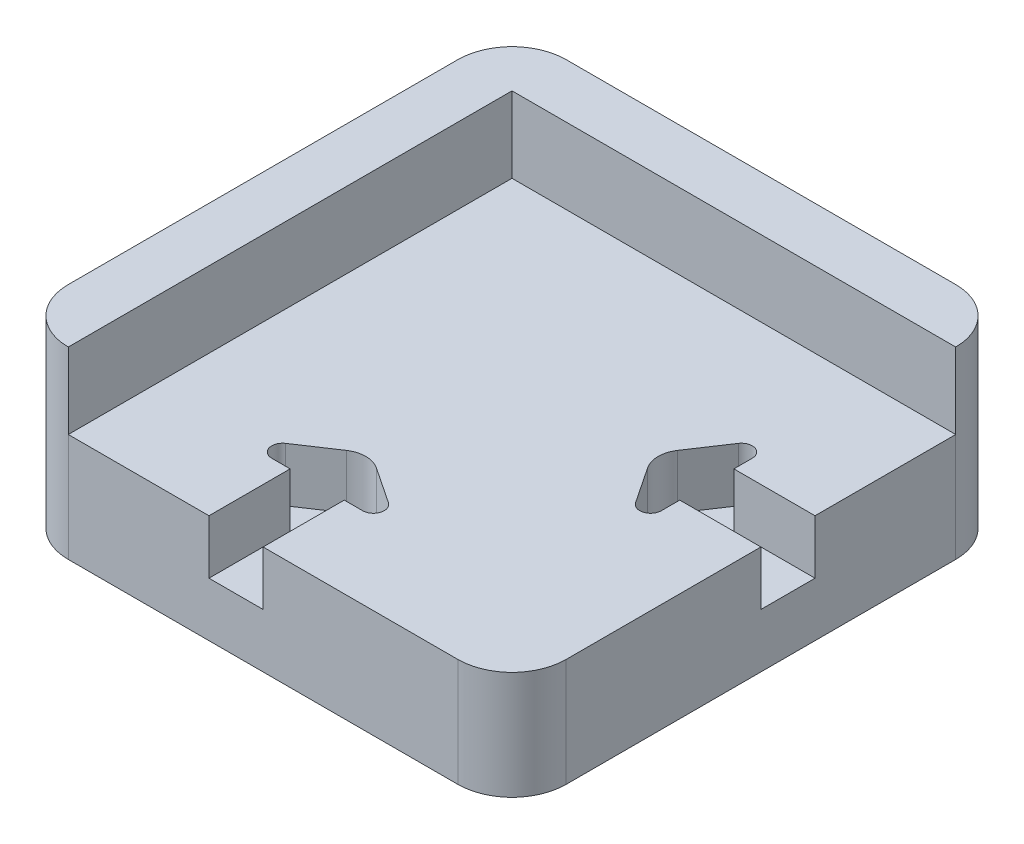
SolidWorks part; units mm, degrees
ref_plane "Front Plane" through (0, 0, 0) normal (0, 0, 1) x (1, 0, 0)
ref_plane "Top Plane" through (0, 0, 0) normal (0, 1, 0) x (1, 0, 0)
ref_plane "Right Plane" through (0, 0, 0) normal (1, 0, 0) x (0, 0, -1)
sketch "Sketch1" plane through (0, 0, 0) normal (0, 1, 0) x (1, 0, 0)
  line L1 (-35.4665, 19.9989) -> (56.5335, 19.9989)
  line L2 (-35.4665, 19.9989) -> (-35.4665, -72.0011)
  line L3 (-35.4665, -72.0011) -> (56.5335, -72.0011)
  line L4 (56.5335, 19.9989) -> (56.5335, -72.0011)
  line L5 (-35.4665, 19.9989) -> (-25.4665, 19.9989)
  line L6 (-35.4665, 19.9989) -> (-35.4665, -72.0011)
  line L7 (-35.4665, -72.0011) -> (-25.4665, -72.0011)
  line L8 (-25.4665, 19.9989) -> (-25.4665, -72.0011)
  line L9 (-35.4665, 19.9989) -> (56.5335, 19.9989)
  line L10 (-35.4665, 19.9989) -> (-35.4665, 9.9989)
  line L11 (-35.4665, 9.9989) -> (56.5335, 9.9989)
  line L12 (56.5335, 19.9989) -> (56.5335, 9.9989)
  dimension "D1" = 92
  dimension "D2" = 92
  dimension "D3" = 10
  dimension "D4" = 10
extrude "Boss-Extrude1" add sketch "Sketch1" along normal blind 20 contours L11 L8 L3 L4 | L8 L11 L4 L1 | L2 L11 L8 L1 | L11 L6 L3 L8 region at (-30.4665, 0, -14.9989) region at (15.5335, 0, -14.9989) region at (-30.4665, 0, 31.0011) region at (15.5335, 0, 31.0011)
extrude "Boss-Extrude2" add sketch "Sketch1<3>" along normal blind 34 contours L11 L6 L3 L8 | L2 L11 L8 L1 | L8 L11 L4 L1 region at (-30.4665, 0, -14.9989) region at (15.5335, 0, -14.9989) region at (-30.4665, 0, 31.0011)
sketch "Sketch1<3>" plane through (0, 0, 0) normal (0, 1, 0) x (1, 0, 0) same geometry as "Sketch1"
fillet "Fillet1" radius 10 4 edges at (56.5335, 17, -19.9989) (-35.4665, 17, -19.9989) (-35.4665, 17, 72.0011) (56.5335, 10, 72.0011)
sketch "Sketch5" plane through (0, 20, 0) normal (0, 1, 0) x (1, 0, 0)
  line L0 (-25.4665, -72.0011) -> (46.5335, -72.0011) construction
  line L1 (10.5335, -72.0011) -> (0.5335, -72.0011)
  line L2 (10.5335, -72.0011) -> (10.5335, -57.0011)
  line L3 (10.5335, -57.0011) -> (0.5335, -57.0011)
  line L4 (0.5335, -72.0011) -> (0.5335, -57.0011)
  line L5 (5.5335, -57.0011) -> (5.5335, -47.0011)
  line L6 (0.5335, -57.0011) -> (-9.4665, -57.0011)
  line L7 (-9.4665, -57.0011) -> (5.5335, -47.0011)
  line L8 (10.5335, -57.0011) -> (20.5321, -57.0011)
  line L9 (20.5321, -57.0011) -> (5.5335, -47.0011)
  line M5 (-25.4665, -72.0011) -> (46.5335, -72.0011)
  dimension "D1" = 15
  dimension "D2" = 10
  dimension "D3" = 10
  dimension "D4" = 10
extrude "Cut-Extrude2" cut sketch "Sketch5" against normal blind 10 contours L8 L9 L5 L3 | L7 L6 L3 L5 | L4 L2 L3 M5 region at (5.5335, 20, 64.5011) region at (10.533, 20, 53.6677) region at (0.5335, 20, 53.6677)
sketch "Sketch6" plane through (0, 20, 0) normal (0, 1, 0) x (1, 0, 0)
  line L0 (56.5335, 9.9989) -> (56.5335, -62.0011) construction
  line L1 (56.5335, -26.0011) -> (41.5335, -26.0011)
  line L2 (56.5335, -26.0011) -> (56.5335, -16.0011)
  line L3 (56.5335, -16.0011) -> (41.5335, -16.0011)
  line L4 (41.5335, -26.0011) -> (41.5335, -16.0011)
  line L5 (41.5335, -16.0011) -> (41.5335, -6.0011)
  line L6 (41.5335, -26.0011) -> (41.5335, -36.0011)
  line L8 (41.5335, -21.0011) -> (31.5335, -21.0011)
  line L9 (41.5335, -6.0011) -> (31.5335, -21.0011)
  line L10 (41.5335, -36.0011) -> (31.5335, -21.0011)
  line M9 (56.5335, -62.0011) -> (56.5335, 9.9989)
  dimension "D1" = 15
  dimension "D2" = 10
  dimension "D3" = 10
  dimension "D4" = 10
  dimension "D5" = 10
extrude "Cut-Extrude3" cut sketch "Sketch6" against normal blind 10 contours L4 L1 L3 M9 | L5 L9 L8 L4 | L10 L6 L4 L8 region at (49.0335, 20, 21.0011) region at (38.2001, 20, 26.0011) region at (38.2001, 20, 16.0011)
fillet "Fillet2" radius 5 2 edges at (31.5335, 15, 21.0011) (5.5335, 15, 47.0011)
fillet "Fillet3" radius 2 4 edges at (41.5335, 15, 6.0011) (41.5335, 15, 36.0011) (20.5321, 15, 57.0011) (-9.4665, 15, 57.0011)
